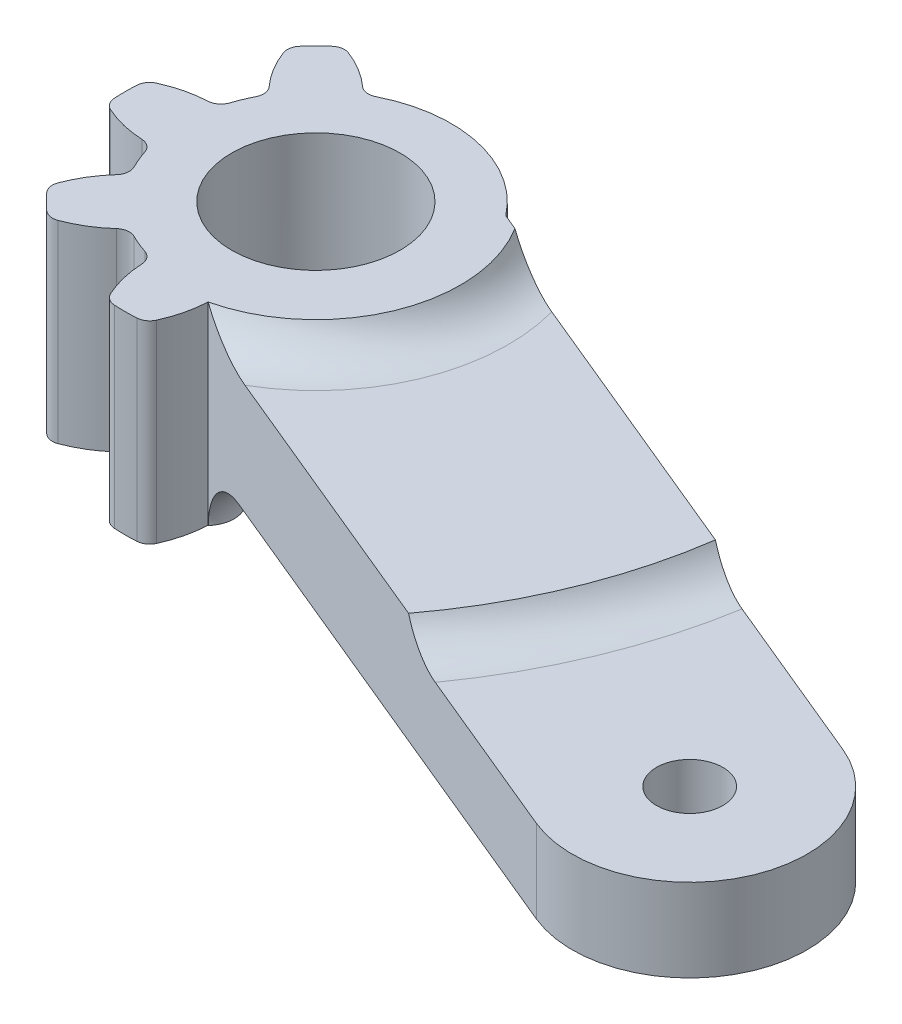
SolidWorks part; units mm, degrees
ref_plane "Front Plane" through (0, 0, 0) normal (0, 0, 1) x (1, 0, 0)
ref_plane "Top Plane" through (0, 0, 0) normal (0, 1, 0) x (1, 0, 0)
ref_plane "Right Plane" through (0, 0, 0) normal (1, 0, 0) x (0, 0, -1)
sketch "Sketch1" plane through (0, 0, 0) normal (0, 1, 0) x (1, 0, 0)
  line L0 (0, -4.9) -> (0, 4.9) construction
  line L3 (-2.9, 4.9) -> (2.9, 4.9) construction
  circle A2 centre (0, 0) radius 5.5 construction
  circle A3 centre (0, 11.8) radius 6.3 construction
  circle A4 centre (0, 11.8) radius 5.5 construction
  circle A5 centre (0, 11.8) radius 4.9 construction
  arc A7 (-4.377, 2.2027) -> (-4.6525, 1.5375) centre (0, 0) ccw
  arc A8 (-0.8329, 6.5956) -> (-1.195, 5.1026) centre (2.9, 4.9) ccw
  arc A9 (1.195, 5.1026) -> (0.8329, 6.5956) centre (-2.9, 4.9) ccw
  arc A10 (0.4072, 6.888) -> (-0.4072, 6.888) centre (0, 0) ccw
  arc A11 (4.4531, 2.7631) -> (5.2528, 4.0748) centre (1.4142, 5.5154) ccw
  arc A12 (5.1585, 4.5826) -> (4.5826, 5.1585) centre (0, 0) ccw
  arc A13 (4.0748, 5.2528) -> (2.7631, 4.4531) centre (5.5154, 1.4142) ccw
  arc A14 (5.1026, -1.195) -> (6.5956, -0.8329) centre (4.9, 2.9) ccw
  arc A15 (6.888, -0.4072) -> (6.888, 0.4072) centre (0, 0) ccw
  arc A16 (6.5956, 0.8329) -> (5.1026, 1.195) centre (4.9, -2.9) ccw
  arc A17 (2.7631, -4.4531) -> (4.0748, -5.2528) centre (5.5154, -1.4142) ccw
  arc A18 (4.5826, -5.1585) -> (5.1585, -4.5826) centre (0, 0) ccw
  arc A19 (5.2528, -4.0748) -> (4.4531, -2.7631) centre (1.4142, -5.5154) ccw
  arc A20 (-1.195, -5.1026) -> (-0.8329, -6.5956) centre (2.9, -4.9) ccw
  arc A21 (-0.4072, -6.888) -> (0.4072, -6.888) centre (0, 0) ccw
  arc A22 (0.8329, -6.5956) -> (1.195, -5.1026) centre (-2.9, -4.9) ccw
  arc A23 (-4.4531, -2.7631) -> (-5.2528, -4.0748) centre (-1.4142, -5.5154) ccw
  arc A24 (-5.1585, -4.5826) -> (-4.5826, -5.1585) centre (0, 0) ccw
  arc A25 (-4.0748, -5.2528) -> (-2.7631, -4.4531) centre (-5.5154, -1.4142) ccw
  arc A26 (-5.1026, 1.195) -> (-6.5956, 0.8329) centre (-4.9, -2.9) ccw
  arc A27 (-6.888, 0.4072) -> (-6.888, -0.4072) centre (0, 0) ccw
  arc A28 (-6.5956, -0.8329) -> (-5.1026, -1.195) centre (-4.9, 2.9) ccw
  arc A29 (-2.7631, 4.4531) -> (-4.0748, 5.2528) centre (-5.5154, 1.4142) ccw
  arc A30 (-4.5826, 5.1585) -> (-5.1585, 4.5826) centre (0, 0) ccw
  arc A31 (-5.2528, 4.0748) -> (-4.4531, 2.7631) centre (-1.4142, 5.5154) ccw
  arc A32 (-4.6525, -1.5375) -> (-4.377, -2.2027) centre (0, 0) ccw
  arc A33 (-2.2027, -4.377) -> (-1.5375, -4.6525) centre (0, 0) ccw
  arc A34 (1.5375, -4.6525) -> (2.2027, -4.377) centre (0, 0) ccw
  arc A35 (4.377, -2.2027) -> (4.6525, -1.5375) centre (0, 0) ccw
  arc A36 (4.6525, 1.5375) -> (4.377, 2.2027) centre (0, 0) ccw
  arc A37 (2.2027, 4.377) -> (1.5375, 4.6525) centre (0, 0) ccw
  arc A38 (-1.5375, 4.6525) -> (-2.2027, 4.377) centre (0, 0) ccw
  arc A39 (4.4531, -2.7631) -> (4.377, -2.2027) centre (4.8236, -2.4274) cw
  arc A40 (2.7631, -4.4531) -> (2.2027, -4.377) centre (2.4274, -4.8236) ccw
  arc A41 (-0.8329, -6.5956) -> (-0.4072, -6.888) centre (-0.3777, -6.3888) ccw
  arc A42 (0.4072, -6.888) -> (0.8329, -6.5956) centre (0.3777, -6.3888) ccw
  arc A43 (4.0748, -5.2528) -> (4.5826, -5.1585) centre (4.2505, -4.7847) ccw
  arc A44 (5.1585, -4.5826) -> (5.2528, -4.0748) centre (4.7847, -4.2505) ccw
  arc A45 (6.5956, -0.8329) -> (6.888, -0.4072) centre (6.3888, -0.3777) ccw
  arc A46 (5.1026, -1.195) -> (4.6525, -1.5375) centre (5.1273, -1.6944) ccw
  arc A47 (4.4531, 2.7631) -> (4.377, 2.2027) centre (4.8236, 2.4274) ccw
  arc A48 (5.1026, 1.195) -> (4.6525, 1.5375) centre (5.1273, 1.6944) cw
  arc A49 (6.888, 0.4072) -> (6.5956, 0.8329) centre (6.3888, 0.3777) ccw
  arc A50 (2.7631, 4.4531) -> (2.2027, 4.377) centre (2.4274, 4.8236) cw
  arc A51 (5.2528, 4.0748) -> (5.1585, 4.5826) centre (4.7847, 4.2505) ccw
  arc A52 (4.5826, 5.1585) -> (4.0748, 5.2528) centre (4.2505, 4.7847) ccw
  arc A53 (0.8329, 6.5956) -> (0.4072, 6.888) centre (0.3777, 6.3888) ccw
  arc A54 (-0.8329, 6.5956) -> (-0.4072, 6.888) centre (-0.3777, 6.3888) cw
  arc A55 (-1.195, 5.1026) -> (-1.5375, 4.6525) centre (-1.6944, 5.1273) cw
  arc A56 (-1.195, -5.1026) -> (-1.5375, -4.6525) centre (-1.6944, -5.1273) ccw
  arc A57 (-2.7631, -4.4531) -> (-2.2027, -4.377) centre (-2.4274, -4.8236) cw
  arc A58 (-5.2528, -4.0748) -> (-5.1585, -4.5826) centre (-4.7847, -4.2505) ccw
  arc A59 (-6.888, -0.4072) -> (-6.5956, -0.8329) centre (-6.3888, -0.3777) ccw
  arc A60 (-4.4531, -2.7631) -> (-4.377, -2.2027) centre (-4.8236, -2.4274) ccw
  arc A61 (-5.1026, -1.195) -> (-4.6525, -1.5375) centre (-5.1273, -1.6944) cw
  arc A62 (-6.5956, 0.8329) -> (-6.888, 0.4072) centre (-6.3888, 0.3777) ccw
  arc A63 (-5.1026, 1.195) -> (-4.6525, 1.5375) centre (-5.1273, 1.6944) ccw
  arc A64 (-4.4531, 2.7631) -> (-4.377, 2.2027) centre (-4.8236, 2.4274) cw
  arc A65 (-5.1585, 4.5826) -> (-5.2528, 4.0748) centre (-4.7847, 4.2505) ccw
  arc A66 (-4.0748, 5.2528) -> (-4.5826, 5.1585) centre (-4.2505, 4.7847) ccw
  arc A67 (-2.7631, 4.4531) -> (-2.2027, 4.377) centre (-2.4274, 4.8236) ccw
  arc A68 (1.195, 5.1026) -> (1.5375, 4.6525) centre (1.6944, 5.1273) ccw
  arc A69 (1.195, -5.1026) -> (1.5375, -4.6525) centre (1.6944, -5.1273) cw
  arc A70 (-4.5826, -5.1585) -> (-4.0748, -5.2528) centre (-4.2505, -4.7847) ccw
  point P14 (0, 4.9)
  point P92 (-1.1973, 4.7515)
  point P119 (1.1973, 4.7515)
  dimension "D4" = 11
  dimension "D5" = 11
  dimension "D2" = 9.8
  dimension "D3" = 9.8
  dimension "D6" = 6.9
  dimension "D8" = 4.1
  dimension "D9" = 4.1
  dimension "D11" = 0.5
  dimension "D12" = 0.5
  dimension "D13" = 0.5
  dimension "D1" = 11.8
  dimension "D7" = 5.8
  dimension "D10" = 8
extrude "Boss-Extrude1" add sketch "Sketch1" along normal blind 7
sketch "Sketch2" plane through (0, 7, 0) normal (0, 1, 0) x (1, 0, 0)
  line L0 (0, 0) -> (16.682, -6.9099) construction
  line L3 (0, 0) -> (0, 4.25) construction
  line L4 (-2.5848, 6.3976) -> (-1.8356, 4.5432)
  line L5 (1.8356, -4.5432) -> (2.5848, -6.3976)
  line L6 (-1.8356, 4.5432) -> (1.8356, -4.5432) construction
  arc A2 (1.8356, -4.5432) -> (-1.8356, 4.5432) centre (0, 0) ccw
  arc A3 (2.5848, -6.3976) -> (-2.5848, 6.3976) centre (0, 0) ccw
  arc A4 (5.1585, 4.5826) -> (4.5826, 5.1585) centre (0, 0) ccw construction
  arc A5 (2.2027, 4.377) -> (1.5375, 4.6525) centre (0, 0) ccw construction
  circle A6 centre (0, 0) radius 3.05
  dimension "D2" = 22
  dimension "D3" = 6.1
  dimension "D1" = 112.5
extrude "Cut-Extrude1" cut sketch "Sketch2" against normal blind 10
sketch "Sketch4" plane through (0, 7, 0) normal (0, 1, 0) x (1, 0, 0)
  line L0 (-4.527, 1.8751) -> (0, 0) construction
  line L1 (0, 0) -> (23.097, -9.5671) construction
  line L2 (1.6264, 3.9265) -> (24.7234, -5.6406)
  line L3 (-1.6264, -3.9265) -> (21.4706, -13.4936)
  arc A0 (-4.377, 2.2027) -> (-4.6525, 1.5375) centre (0, 0) ccw construction
  arc A1 (1.6264, 3.9265) -> (-1.6264, -3.9265) centre (0, 0) ccw
  arc A2 (21.4706, -13.4936) -> (24.7234, -5.6406) centre (23.097, -9.5671) ccw
  circle A3 centre (23.097, -9.5671) radius 1.2
  circle A4 centre (0, 0) radius 3.05
  circle A5 centre (0, 0) radius 3.05 construction
  point P6 (11.5485, -4.7835)
  dimension "D1" = 8.5
  dimension "D2" = 2.4
  dimension "D3" = 25
extrude "Boss-Extrude2" add sketch "Sketch4" against normal up to surface (7 mm away) up to face at (-3.3599, 0, 1.3917)
sketch "Sketch6" plane through (0, 0, 0) normal (0, -1, 0) x (1, 0, 0)
  line L0 (12.5186, 5.1854) -> (0, 0) construction
  line L1 (14.4587, 5.989) -> (-2.8178, -1.1672) construction
  line L2 (24.7234, 5.6406) -> (3.8795, -2.9932) construction
  line L3 (-0.9668, 2.8927) -> (11.8529, 7.1771)
  line L5 (13.4563, 3.3063) -> (1.3619, -2.7291)
  arc A0 (-0.9668, 2.8927) -> (1.3619, -2.7291) centre (0, 0) ccw
  circle A1 centre (0, 0) radius 3.05 construction
  arc A2 (13.4563, 3.3063) -> (11.8529, 7.1771) centre (12.5186, 5.1854) ccw
  dimension "D1" = 4.2
  dimension "D2" = 18.7
extrude "Cut-Extrude2" cut sketch "Sketch6" against normal blind 5.5
sketch "Sketch7" plane through (0, 0, 0) normal (0, -1, 0) x (1, 0, 0)
  line L0 (0, 0) -> (23.097, 9.5671) construction
  line L1 (1.2064, 5.0999) -> (21.4706, 13.4936)
  line L2 (4.4592, -2.7531) -> (24.7234, 5.6406)
  line L3 (24.7234, 5.6406) -> (3.8795, -2.9932) construction
  line L4 (1.1954, 5.0953) -> (21.4706, 13.4936) construction
  arc A0 (4.4592, -2.7531) -> (1.2064, 5.0999) centre (0, 0) ccw
  arc A2 (24.7234, 5.6406) -> (21.4706, 13.4936) centre (23.097, 9.5671) ccw
  arc A3 (24.7234, 5.6406) -> (21.4706, 13.4936) centre (23.097, 9.5671) ccw construction
  point P1 (4.2187, -3.1092)
  point P3 (11.5485, 4.7835)
  point P15 (0.5575, 5.2109)
extrude "Cut-Extrude3" cut sketch "Sketch7" against normal blind 2
sketch "Sketch8" plane through (0, 7, 0) normal (0, 1, 0) x (1, 0, 0)
  line L0 (0, 0) -> (23.097, -9.5671) construction
  line L1 (4.4482, 2.7577) -> (24.7234, -5.6406)
  line L2 (1.1954, -5.0953) -> (21.4706, -13.4936)
  line L3 (24.7234, -5.6406) -> (3.8795, 2.9932) construction
  line L6 (1.1954, -5.0953) -> (21.4706, -13.4936) construction
  arc A0 (1.1954, -5.0953) -> (4.4482, 2.7577) centre (0, 0) ccw
  arc A2 (21.4706, -13.4936) -> (24.7234, -5.6406) centre (23.097, -9.5671) ccw
  arc A3 (21.4706, -13.4936) -> (24.7234, -5.6406) centre (23.097, -9.5671) ccw construction
  point P1 (-1.837, -4.7835)
  point P4 (11.5485, -4.7835)
  point P7 (2.8773, 4.3718)
  point P19 (0, -5.2337)
extrude "Cut-Extrude4" cut sketch "Sketch8" against normal blind 1
sketch "Sketch9" plane through (0, 6, 0) normal (0, 1, 0) x (1, 0, 0)
  line L0 (0, 0) -> (23.097, -9.5671) construction
  line L1 (16.8336, -2.3725) -> (24.7234, -5.6406)
  line L2 (13.5808, -10.2255) -> (21.4706, -13.4936)
  line L3 (24.7234, -5.6406) -> (4.4482, 2.7577) construction
  line L4 (1.1954, -5.0953) -> (21.4706, -13.4936) construction
  arc A0 (13.5808, -10.2255) -> (16.8336, -2.3725) centre (0, 0) ccw
  arc A2 (21.4706, -13.4936) -> (24.7234, -5.6406) centre (23.097, -9.5671) ccw
  arc A3 (21.4706, -13.4936) -> (24.7234, -5.6406) centre (23.097, -9.5671) ccw construction
  point P1 (10.9137, -13.0343)
  point P3 (11.5485, -4.7835)
  point P6 (16.7924, 2.6485)
  dimension "D1" = 34
extrude "Cut-Extrude5" cut sketch "Sketch9" against normal blind 1
fillet "Fillet2" radius 1 2 edges at (5.1751, 1, -0.8262) (3.0752, 1, 4.2435)
fillet "Fillet3" radius 2 2 edges at (3.9665, 2, -1.9371) (1.435, 2, 4.1745)
fillet "Fillet4" radius 2 2 edges at (15.706, 5, 6.5056) (4.8353, 6, 2.0028)
